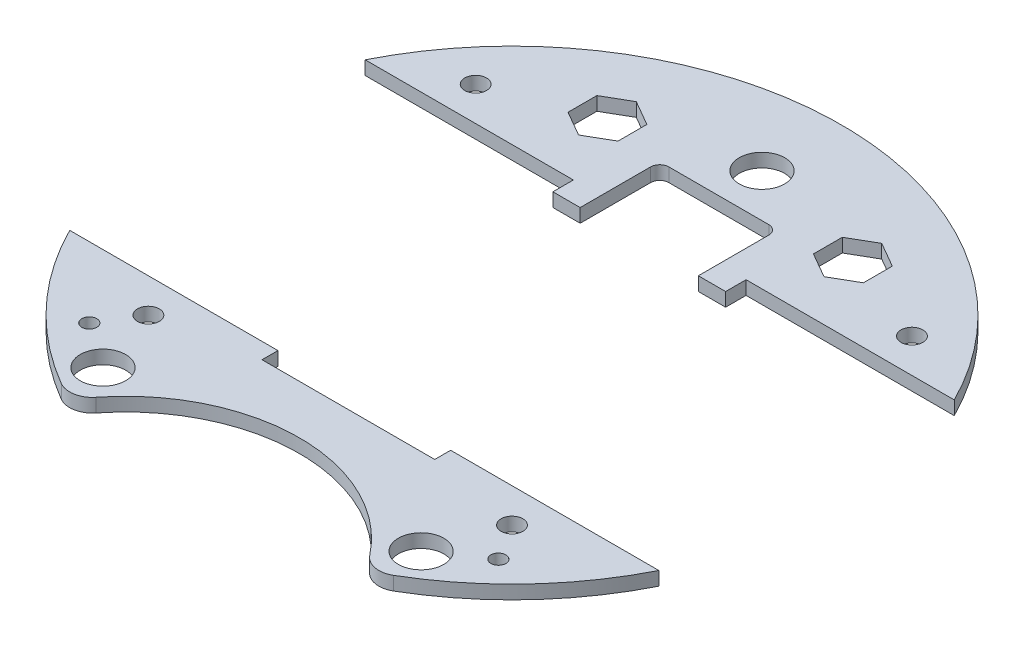
SolidWorks part; units mm, degrees
material "Acrylic (Medium-high impact)"
ref_plane "Front Plane" through (0, 0, 0) normal (0, 0, 1) x (1, 0, 0)
ref_plane "Top Plane" through (0, 0, 0) normal (0, 1, 0) x (1, 0, 0)
ref_plane "Right Plane" through (0, 0, 0) normal (1, 0, 0) x (0, 0, -1)
sketch "Sketch1" plane through (0, 0, 0) normal (0, 1, 0) x (1, 0, 0)
  line L0 (0, -85) -> (-32.4891, -64.8129) construction
  line L1 (0, -85) -> (0, 0) construction
  arc A0 (36.5434, -62.6165) -> (-36.5434, -62.6165) centre (0, 0) ccw
  arc A1 (30.0898, -61.3851) -> (-30.0898, -61.3851) centre (0, -85) ccw
  arc A2 (-30.0898, -61.3851) -> (-36.5434, -62.6165) centre (-34.0231, -58.2982) cw
  arc A3 (36.5434, -62.6165) -> (30.0898, -61.3851) centre (34.0231, -58.2982) cw
  dimension "D1" = 145
  dimension "D2" = 76.5
  dimension "D4" = 5
  dimension "D3" = 85
extrude "Boss-Extrude1" add sketch "Sketch1" along normal blind 3
sketch "solenoid placement" plane through (0, 3, 0) normal (0, 1, 0) x (1, 0, 0)
  line L4 (-19, -36) -> (19, -36)
  line L5 (-19, 28) -> (-19, -36)
  line L6 (19, 28) -> (-19, 28)
  line L7 (19, -36) -> (19, 28)
  line L8 (-19, -36) -> (19, -36)
  line L9 (-19, 28) -> (-19, -36)
  line L10 (19, 28) -> (-19, 28)
  line L11 (19, -36) -> (19, 28)
  dimension "D1" = 0
extrude "Cut-Extrude1" cut sketch "solenoid placement" against normal through all
sketch "Sketch4" plane through (0, 3, 0) normal (0, 1, 0) x (1, 0, 0)
  line L8 (13, 28) -> (13, 43.5)
  line L9 (-13, 28) -> (13, 28)
  line L10 (-13, 43.5) -> (-13, 28)
  line L11 (11, 45.5) -> (-11, 45.5)
  line L28 (13, 28) -> (13, 43.5)
  line L29 (-13, 28) -> (13, 28)
  line L30 (-13, 43.5) -> (-13, 28)
  line L31 (11, 45.5) -> (-11, 45.5)
  arc A4 (-11, 45.5) -> (-13, 43.5) centre (-11, 43.5) ccw
  arc A5 (13, 43.5) -> (11, 45.5) centre (11, 43.5) ccw
  arc A14 (-11, 45.5) -> (-13, 43.5) centre (-11, 43.5) ccw
  arc A15 (13, 43.5) -> (11, 45.5) centre (11, 43.5) ccw
  dimension "D1" = 0
extrude "Cut-Extrude4" cut sketch "Sketch4" against normal through all
sketch "Sketch5" plane through (0, 3, 0) normal (0, 1, 0) x (1, 0, 0)
  line L12 (-21.5, 51.1754) -> (-27, 54.3509)
  line L13 (-27, 54.3509) -> (-32.5, 51.1754)
  line L14 (-32.5, 51.1754) -> (-32.5, 44.8246)
  line L15 (-32.5, 44.8246) -> (-27, 41.6491)
  line L16 (-27, 41.6491) -> (-21.5, 44.8246)
  line L17 (-21.5, 44.8246) -> (-21.5, 51.1754)
  line L18 (-21.5, 51.1754) -> (-27, 54.3509)
  line L19 (-27, 54.3509) -> (-32.5, 51.1754)
  line L20 (-32.5, 51.1754) -> (-32.5, 44.8246)
  line L21 (-32.5, 44.8246) -> (-27, 41.6491)
  line L22 (-27, 41.6491) -> (-21.5, 44.8246)
  line L23 (-21.5, 44.8246) -> (-21.5, 51.1754)
  line L24 (21.5, 51.1754) -> (21.5, 44.8246)
  line L25 (21.5, 44.8246) -> (27, 41.6491)
  line L26 (27, 41.6491) -> (32.5, 44.8246)
  line L27 (32.5, 44.8246) -> (32.5, 51.1754)
  line L28 (32.5, 51.1754) -> (27, 54.3509)
  line L29 (27, 54.3509) -> (21.5, 51.1754)
  line L42 (21.5, 51.1754) -> (21.5, 44.8246)
  line L43 (21.5, 44.8246) -> (27, 41.6491)
  line L44 (27, 41.6491) -> (32.5, 44.8246)
  line L45 (32.5, 44.8246) -> (32.5, 51.1754)
  line L46 (32.5, 51.1754) -> (27, 54.3509)
  line L47 (27, 54.3509) -> (21.5, 51.1754)
  dimension "D1" = 0
  dimension "D2" = 0
extrude "Cut-Extrude5" cut sketch "Sketch5" against normal through all
sketch "Sketch6" plane through (0, 3, 0) normal (0, 1, 0) x (1, 0, 0)
  circle A1 centre (40, -40) radius 2.4
  circle A2 centre (40, -40) radius 2.4
  circle A3 centre (-40, -40) radius 2.4
  circle A4 centre (-40, -40) radius 2.4
  circle A5 centre (48, 40) radius 2.4
  circle A6 centre (48, 40) radius 2.4
  circle A7 centre (-48, 40) radius 2.4
  circle A8 centre (-48, 40) radius 2.4
  dimension "D1" = 0
  dimension "D2" = 0
  dimension "D3" = 0
  dimension "D4" = 0
extrude "Cut-Extrude6" cut sketch "Sketch6" against normal through all
sketch "Sketch3" plane through (0, 3, 0) normal (0, 1, 0) x (1, 0, 0)
  line L0 (-19, 28) -> (-19, 32.5)
  line L1 (72.5, -32.5) -> (-72.5, -32.5)
  line L2 (72.5, -32.5) -> (72.5, 32.5)
  line L3 (72.5, 32.5) -> (19, 32.5)
  line L4 (-72.5, -32.5) -> (-72.5, 32.5)
  line L5 (72.5, -32.5) -> (-72.5, 32.5) construction
  line L6 (72.5, 32.5) -> (-72.5, -32.5) construction
  line L7 (-19, 28) -> (19, 28)
  line L8 (19, 28) -> (19, 32.5)
  line L9 (-19, 32.5) -> (-72.5, 32.5)
  line L10 (-19, 28) -> (-19, -36) construction
  line L11 (-13, 28) -> (-19, 28) construction
  arc A0 (36.5434, -62.6165) -> (-36.5434, -62.6165) centre (0, 0) ccw construction
  point P0 (0, 0)
  dimension "D1" = 65
extrude "Cut-Extrude3" cut sketch "Sketch3" against normal through all
sketch "Sketch7" plane through (0, 3, 0) normal (0, 1, 0) x (1, 0, 0)
  circle A1 centre (35, -55) radius 5
  circle A2 centre (35, -55) radius 5
  circle A3 centre (-35, -55) radius 5
  circle A4 centre (-35, -55) radius 5
  dimension "D1" = 0
  dimension "D2" = 0
extrude "Cut-Extrude7" cut sketch "Sketch7" against normal through all
sketch "Sketch8" plane through (0, 3, 0) normal (0, -1, 0) x (1, 0, 0)
  circle A1 centre (0, -55) radius 5
  circle A2 centre (0, -55) radius 5
  dimension "D1" = 0
extrude "Cut-Extrude9" cut sketch "Sketch8" along normal through all
sketch "Sketch9" plane through (0, 3, 0) normal (0, 1, 0) x (1, 0, 0)
  line L0 (0, 0) -> (0, -21.5516) construction
  circle A0 centre (45, -48) radius 1.65
  circle A1 centre (-45, -48) radius 1.65
  point P5 (0, 0)
  dimension "D3" = 3.3
  dimension "D1" = 45
  dimension "D2" = 48
extrude "Cut-Extrude10" cut sketch "Sketch9" against normal through all
equation "\"smallPulleyTeeth\"= 30"
equation "\"largePulleyTeeth\"= 30"
equation "\"eighthThick\"= 3.0mm"
equation "\"sixteenthThick\" = 1.7mm"
equation "\"quarterThick\"=6.0mm"
equation "\"OD\" = 145mm"
equation "\"puckAngle\" = 60.5deg"
equation "\"D1@Sketch1\"=\"OD\""
equation "\"puckDiam\" = 76.5mm"
equation "\"D2@Sketch1\"=\"puckDiam\""
equation "\"D1@Boss-Extrude1\"=\"eighthThick\""
equation "\"axlePress\" = 5.9mm"
equation "\"press\" = 0.2mm"
equation "\"wheelClear\" = 0.3mm"
equation "\"10-32clear\" = 4.8mm"
equation "\"6-32clear\" = 3.3mm"
equation "\"8-32clear\" = 4.0mm"
equation "\"wheelHeight\" = 22mm"
equation "\"wheelWell\" = 65mm"
equation "\"D1@Sketch3\"=\"wheelWell\""
equation "\"puckDist\" = 85mm"
equation "\"scoopFillet\" = 5mm"
equation "\"4-40clear\" = 3.0mm"
equation "\"D3@Sketch1\"=\"puckDist\""
equation "\"D4@Sketch1\"=\"scoopFillet\""
equation "\"D3@Sketch9\"=\"6-32clear\""
